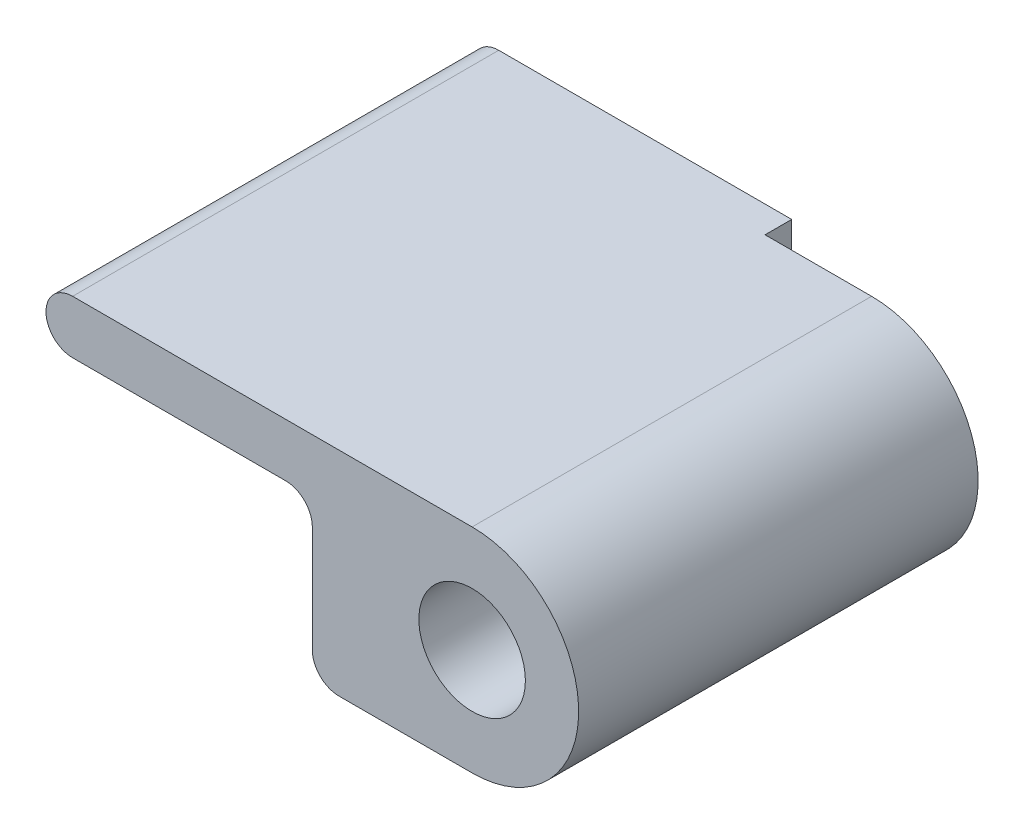
SolidWorks part; units mm, degrees
material "ABS"
ref_plane "Front Plane" through (0, 0, 0) normal (0, 0, 1) x (1, 0, 0)
ref_plane "Top Plane" through (0, 0, 0) normal (0, 1, 0) x (1, 0, 0)
ref_plane "Right Plane" through (0, 0, 0) normal (1, 0, 0) x (0, 0, -1)
sketch "Sketch1" plane through (0, 0, 0) normal (0, 0, 1) x (1, 0, 0)
  line L0 (-6.35, 0) -> (-6.35, 3.175) construction
  line L1 (0, 3.175) -> (-25.4, 3.175)
  line L2 (-25.4, 3.175) -> (-25.4, 6.35)
  line L3 (-25.4, 6.35) -> (0, 6.35)
  line L4 (0, -6.35) -> (-6.35, -6.35)
  line L5 (-6.35, 0) -> (-6.35, -6.35) construction
  line L6 (-6.35, -6.35) -> (-9.525, -6.35)
  line L7 (-9.525, -6.35) -> (-9.525, 3.175)
  circle A0 centre (0, 0) radius 6.35
  circle A1 centre (0, 0) radius 3.175
  dimension "D1" = 6.35
  dimension "D2" = 12.7
  dimension "D3" = 25.4
extrude "Boss-Extrude1" add sketch "Sketch1" along normal blind 25.4 contours A0 L3 L2 L1 | A1 A0 | A0 L1 L7 L6 L4 region at (-14.613, 4.8143, 0) region at (-7.243, -2.2276, 0) region at (-3.0852, 5.3437, 0)
sketch "Sketch2" plane through (0, 0, 25.4) normal (0, 0, 1) x (1, 0, 0)
  line L0 (-25.4, 6.35) -> (0, 6.35) construction
  line L1 (6.35, -6.35) -> (-6.35, -6.35)
  line L2 (6.35, -6.35) -> (6.35, 6.35)
  line L3 (6.35, 6.35) -> (-6.35, 6.35)
  line L4 (-6.35, -6.35) -> (-6.35, 6.35)
  line L5 (6.35, -6.35) -> (-6.35, 6.35) construction
  line L6 (6.35, 6.35) -> (-6.35, -6.35) construction
  arc A0 (0, -6.35) -> (0, 6.35) centre (0, 0) ccw construction
  point P0 (0, 0)
extrude "Cut-Extrude1" cut sketch "Sketch2" along normal blind 1.5875 from surface starting at face at (-10.5833, 1.0583, 0)
fillet "Fillet1" radius 1.5875 4 edges at (-9.525, -6.35, 12.7) (-9.525, 3.175, 12.7) (-25.4, 6.35, 12.7) (-25.4, 3.175, 12.7)
